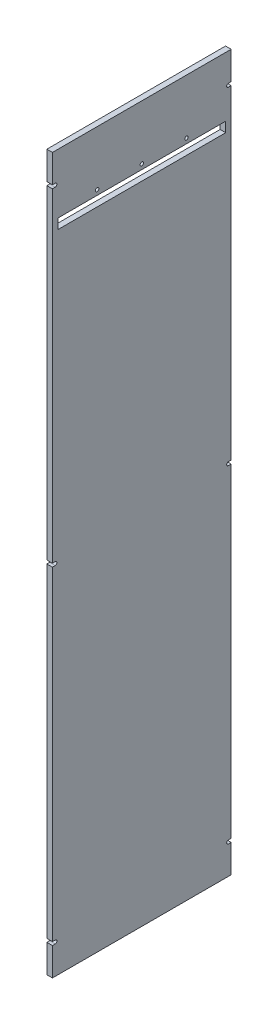
SolidWorks part; units mm, degrees
ref_plane "Front Plane" through (0, 0, 0) normal (0, 0, 1) x (1, 0, 0)
ref_plane "Top Plane" through (0, 0, 0) normal (0, 1, 0) x (1, 0, 0)
ref_plane "Right Plane" through (0, 0, 0) normal (1, 0, 0) x (0, 0, -1)
sketch "Sketch1" plane through (0, 0, 0) normal (0, 1, 0) x (1, 0, 0)
  line L1 (0, 0) -> (4.7625, 0)
  line L2 (0, 0) -> (0, 152.4)
  line L3 (0, 152.4) -> (4.7625, 152.4)
  line L4 (4.7625, 0) -> (4.7625, 152.4)
  dimension "D1" = 152.4
  dimension "D2" = 4.7625
extrude "Boss-Extrude1" add sketch "Sketch1" along normal blind 609.6
sketch "Sketch2" plane through (4.7625, 0, 0) normal (1, 0, 0) x (0, 0, -1)
  line L0 (0, 609.6) -> (152.4, 609.6) construction
  line L1 (147.7645, 550.291) -> (4.6355, 550.291)
  line L2 (147.7645, 550.291) -> (147.7645, 558.8)
  line L3 (147.7645, 558.8) -> (4.6355, 558.8)
  line L4 (4.6355, 550.291) -> (4.6355, 558.8)
  line L5 (76.2, 609.6) -> (76.2, 527.6475) construction
  line L6 (152.4, 609.6) -> (152.4, 0) construction
  dimension "D1" = 8.509
  dimension "D2" = 143.129
  dimension "D3" = 50.8
  dimension "D4" = 4.6355
extrude "Cut-Extrude1" cut sketch "Sketch2" against normal through all
hole_wizard "#4 Clearance Hole1" positions "Sketch9" profile "Sketch10" hole size "#4" standard "ANSI Inch" end condition through all
sketch "Sketch9" plane through (4.7625, 0, 0) normal (1, 0, 0) x (0, 0, -1)
  line L2 (76.2, 609.6) -> (76.2, 510.9761) construction
  line L3 (0, 609.6) -> (152.4, 609.6) construction
  line L5 (147.7645, 558.8) -> (4.6355, 558.8) construction
  line L6 (76.2, 563.0545) -> (38.1, 563.0545) construction
  line L8 (76.2, 563.0545) -> (114.3, 563.0545) construction
  point P17 (76.2, 563.0545)
  point P29 (38.1, 563.0545)
  point P34 (114.3, 563.0545)
  dimension "D1" = 4.2545
  dimension "D2" = 38.1
  dimension "D3" = 38.1
sketch "Sketch10" plane through (4.7625, 563.0545, -114.3) normal (0, 1, 0) x (0, 0, -1)
  line L0 (0, 0) -> (0, 4.7625)
  line L1 (0, 4.7625) -> (1.4732, 4.7625)
  line L2 (1.4732, 4.7625) -> (1.4732, 0)
  line L5 (1.4732, 0) -> (0, 0)
  line L11 (0, -6.35) -> (0, 107.95) construction
  dimension "Thru Hole Dia." = 2.9464
  dimension "Thru Hole Depth" = 4.7625
sketch "Sketch12" plane through (4.7625, 0, 0) normal (1, 0, 0) x (0, 0, -1)
  line L0 (150.0188, 0) -> (150.0188, 609.6) construction
  line L1 (0, 0) -> (152.4, 0) construction
  line L2 (0, 609.6) -> (152.4, 609.6) construction
  line L3 (2.3813, 0) -> (2.3813, 609.6) construction
  line L4 (152.4, 609.6) -> (152.4, 0) construction
  line L5 (0, 609.6) -> (0, 0) construction
  line L6 (152.4, 25.4) -> (0, 25.4) construction
  line L7 (150.0188, 23.9395) -> (152.4, 23.9395)
  line L8 (150.0188, 26.8605) -> (152.4, 26.8605)
  line L9 (152.4, 23.9395) -> (152.4, 26.8605)
  line L10 (2.3812, 23.9395) -> (0, 23.9395)
  line L11 (2.3812, 26.8605) -> (0, 26.8605)
  line L12 (0, 23.9395) -> (0, 26.8605)
  line L13 (0, 303.3395) -> (0, 306.2605)
  line L14 (2.3812, 303.3395) -> (0, 303.3395)
  line L15 (2.3812, 306.2605) -> (0, 306.2605)
  line L16 (152.4, 303.3395) -> (152.4, 306.2605)
  line L17 (150.0188, 303.3395) -> (152.4, 303.3395)
  line L18 (150.0188, 306.2605) -> (152.4, 306.2605)
  line L19 (0, 582.7395) -> (0, 585.6605)
  line L20 (2.3812, 582.7395) -> (0, 582.7395)
  line L21 (2.3812, 585.6605) -> (0, 585.6605)
  line L22 (152.4, 582.7395) -> (152.4, 585.6605)
  line L23 (150.0188, 582.7395) -> (152.4, 582.7395)
  line L24 (150.0188, 585.6605) -> (152.4, 585.6605)
  arc A0 (150.0188, 26.8605) -> (150.0188, 23.9395) centre (150.0188, 25.4) ccw
  arc A1 (2.3812, 23.9395) -> (2.3812, 26.8605) centre (2.3812, 25.4) ccw
  arc A2 (2.3812, 303.3395) -> (2.3812, 306.2605) centre (2.3812, 304.8) ccw
  arc A3 (150.0188, 306.2605) -> (150.0188, 303.3395) centre (150.0188, 304.8) ccw
  arc A4 (2.3812, 582.7395) -> (2.3812, 585.6605) centre (2.3812, 584.2) ccw
  arc A5 (150.0188, 585.6605) -> (150.0188, 582.7395) centre (150.0188, 584.2) ccw
  dimension "D4" = 3
  dimension "D1" = 2.3813
  dimension "D2" = 2.3813
  dimension "D3" = 25.4
extrude "Cut-Extrude2" cut sketch "Sketch12" against normal through all
